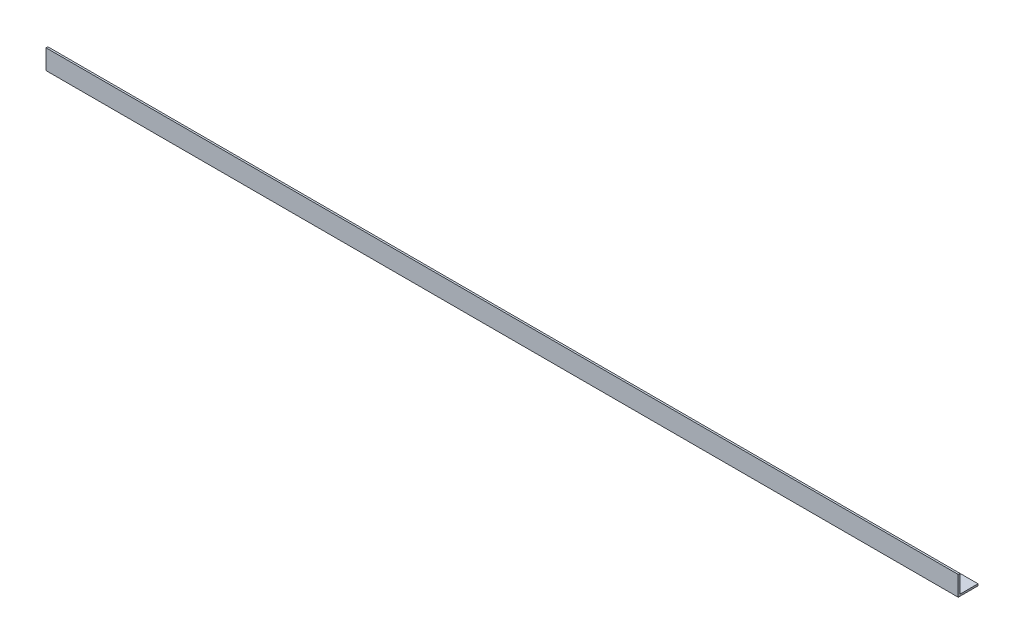
SolidWorks part; units mm, degrees
ref_plane "Спереди" through (0, 0, 0) normal (0, 0, 1) x (1, 0, 0)
ref_plane "Сверху" through (0, 0, 0) normal (0, 1, 0) x (1, 0, 0)
ref_plane "Справа" through (0, 0, 0) normal (1, 0, 0) x (0, 0, -1)
sketch "Эскиз1" plane through (0, 0, 0) normal (1, 0, 0) x (0, 0, -1)
  line L0 (0, 0) -> (65, 0)
  line L1 (0, 0) -> (0, 65)
extrude "Вытянуть-Тонкостенный1" add sketch "Эскиз1" along normal blind 3000 thin thin type one direction wall 6
